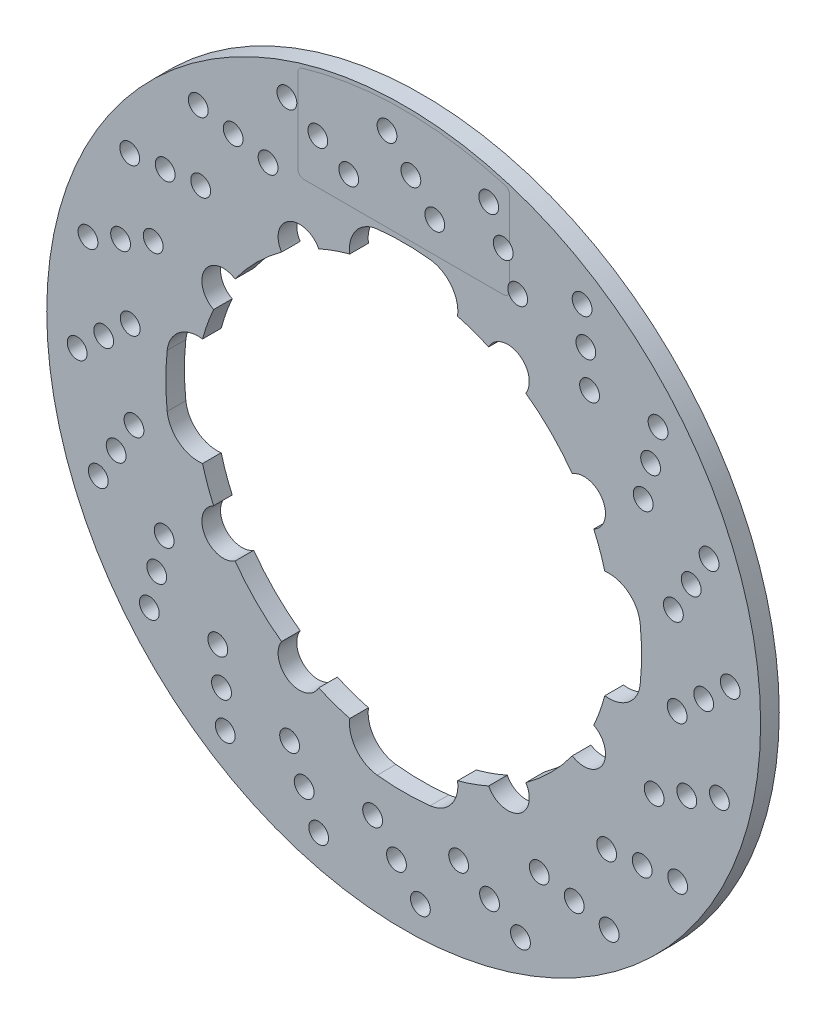
SolidWorks part; units mm, degrees
ref_plane "Front Plane" through (0, 0, 0) normal (0, 0, 1) x (1, 0, 0)
ref_plane "Top Plane" through (0, 0, 0) normal (0, 1, 0) x (1, 0, 0)
ref_plane "Right Plane" through (0, 0, 0) normal (1, 0, 0) x (0, 0, -1)
sketch "Sketch1" plane through (0, 0, 0) normal (0, 0, 1) x (1, 0, 0)
  circle A0 centre (0, 0) radius 114.3
  circle A1 centre (0, 0) radius 76.2
  point P9 (0, 79.756)
  dimension "D1" = 228.6
  dimension "D2" = 152.4
extrude "Boss-Extrude1" add sketch "Sketch1" along normal blind 5.969
sketch "Sketch2" plane through (0, 0, 5.969) normal (0, 0, 1) x (1, 0, 0)
  line L0 (-89.817, 76.2) -> (89.817, 76.2) construction
  line L1 (0, 76.2) -> (-47.8267, 103.8128) construction
  circle A1 centre (0, 0) radius 76.2 construction
  circle A2 centre (0, 0) radius 114.3 construction
  circle A3 centre (-37.395, 97.79) radius 3.175
  circle A4 centre (-27.4963, 92.075) radius 3.175
  circle A5 centre (-17.5976, 86.36) radius 3.175
  point P3 (0, 76.2)
  dimension "D2" = 6.35
  dimension "D3" = 11.43
  dimension "D1" = 30
  dimension "D4" = 11.43
  dimension "D5" = 20.32
extrude "Cut-Extrude1" cut sketch "Sketch2" against normal blind 12.7
sketch "Sketch4" plane through (0, 0, 0) normal (1, 0, 0) x (0, 0, -1)
  line L0 (0, 0) -> (-59.1045, 0) construction
pattern_circular "CirPattern5" count 20 over 360 about axis through (0, 0, 0) along (0, 0, 1) of "Cut-Extrude1"
sketch "Sketch9" plane through (0, 0, 0) normal (0, 0, -1) x (-1, 0, 0)
  line L0 (0, 76.2) -> (0, 42.5) construction
  line L1 (7.427, 41.4562) -> (12.1724, 75.2215)
  line L2 (-7.427, 41.4562) -> (-12.1724, 75.2215)
  circle A0 centre (0, 0) radius 76.2 construction
  arc A1 (-7.427, 41.4562) -> (7.427, 41.4562) centre (0, 42.5) ccw
  circle A2 centre (0, 42.5) radius 4.5
  arc A6 (12.1724, 75.2215) -> (-12.1724, 75.2215) centre (0, 0) ccw
  dimension "D2" = 15
  dimension "D3" = 9
  dimension "D4" = 8
  dimension "D5" = 8
extrude "Boss-Extrude4" add sketch "Sketch9" against normal blind 5.969
fillet "Fillet1" radius 6.35 2 edges at (12.1724, 75.2215, 2.9845) (-12.1724, 75.2215, 2.9845)
pattern_circular "CirPattern8" count 5 over 360 about axis through (0, 0, 0) along (0, 0, 1) of "Fillet1", "Boss-Extrude4"
sketch "Sketch10" plane through (0, 0, 5.969) normal (0, 0, 1) x (1, 0, 0)
  line L0 (0, 114.3) -> (0, 113.03) construction
  circle A0 centre (0, 0) radius 114.3 construction
  circle A1 centre (0, -1.4601) radius 114.4901
  dimension "D2" = 228.9801
  dimension "D1" = 1.27
sketch "Sketch11" plane through (0, 0, 5.969) normal (0, 0, 1) x (1, 0, 0)
  line L0 (0, 113.03) -> (33.9, 113.03) construction
  line L2 (-33.9, 106.4121) -> (-33.9, 79.73)
  line L3 (-31.9, 77.73) -> (31.9, 77.73)
  line L4 (33.9, 106.4121) -> (33.9, 79.73)
  line L6 (0, 114.3) -> (0, 113.03) construction
  arc A0 (-32.4672, 108.33) -> (32.4672, 108.33) centre (0, -1.4601) cw
  circle A1 centre (0, 0) radius 114.3 construction
  arc A2 (-33.9, 79.73) -> (-31.9, 77.73) centre (-31.9, 79.73) ccw
  arc A3 (31.9, 77.73) -> (33.9, 79.73) centre (31.9, 79.73) ccw
  arc A4 (32.4672, 108.33) -> (33.9, 106.4121) centre (31.9, 106.4121) cw
  arc A5 (-32.4672, 108.33) -> (-33.9, 106.4121) centre (-31.9, 106.4121) ccw
  dimension "D3" = 2
  dimension "D6" = 114.4901
  dimension "D1" = 1.27
  dimension "D2" = 67.8
  dimension "D4" = 35.3
  dimension "D5" = 30.6
sketch "Sketch13" plane through (0, 0, 0) normal (0, 0, -1) x (-1, 0, 0)
  line L0 (0, 113.03) -> (33.9, 113.03) construction
  line L2 (-33.9, 106.4121) -> (-33.9, 79.73)
  line L3 (-31.9, 77.73) -> (31.9, 77.73)
  line L4 (33.9, 106.4121) -> (33.9, 79.73)
  line L6 (0, 114.3) -> (0, 113.03) construction
  arc A0 (-32.4672, 108.33) -> (32.4672, 108.33) centre (0, -1.4601) cw
  arc A2 (-33.9, 79.73) -> (-31.9, 77.73) centre (-31.9, 79.73) ccw
  arc A3 (31.9, 77.73) -> (33.9, 79.73) centre (31.9, 79.73) ccw
  arc A4 (32.4672, 108.33) -> (33.9, 106.4121) centre (31.9, 106.4121) cw
  arc A5 (-32.4672, 108.33) -> (-33.9, 106.4121) centre (-31.9, 106.4121) ccw
  dimension "D3" = 2
  dimension "D6" = 114.4901
  dimension "D2" = 67.8
  dimension "D4" = 35.3
  dimension "D5" = 30.6
split line "Split Line1"
split line "Split Line2"
sketch "Sketch14" plane through (0, 0, 0) normal (0, 0, 1) x (1, 0, 0)
  circle A0 centre (0, 0) radius 76.2
  circle A1 centre (0, 0) radius 34.925
  dimension "D1" = 152.4
  dimension "D2" = 69.85
extrude "Boss-Extrude6" add sketch "Sketch14" along normal blind 5.969
sketch "Sketch16" plane through (0, 0, 0) normal (0, 0, 1) x (1, 0, 0)
  line L0 (0, 76.2) -> (0, 42.5) construction
  circle A2 centre (0, 42.5) radius 4.5
  dimension "D3" = 9
extrude "Cut-Extrude3" cut sketch "Sketch16" along normal blind 5.969
pattern_circular "CirPattern9" count 5 over 360 about axis through (0, 0, 5.969) along (0, 0, -1) of "Cut-Extrude3" reverse direction yes
sketch "Sketch17" plane through (0, 0, 0) normal (0, 0, -1) x (-1, 0, 0)
  line L0 (0, 0) -> (0, 66.675) construction
  line L1 (0, 0) -> (-33.3375, 57.7422) construction
  line L2 (0, 0) -> (-57.7422, 33.3375) construction
  circle A0 centre (0, 0) radius 66.675
  circle A1 centre (-33.3375, 57.7422) radius 6.88
  circle A4 centre (-57.7422, 33.3375) radius 6.88
  dimension "D5" = 13.76
  dimension "D1" = 66.675
  dimension "D3" = 30
  dimension "D4" = 30
extrude "Cut-Extrude4" cut sketch "Sketch17" against normal blind 5.969 contours A0 A1 | A0 A4 | A0 A4 | A0 A1 | A4 A0 A1 region at (-0.4578, -0.4578, 0) region at (31.846, 55.1589, 0) region at (34.765, 60.2148, 0) region at (60.2148, 34.765, 0) region at (55.1589, 31.846, 0)
pattern_circular "CirPattern10" count 4 over 360 about axis through (0, 0, 0) along (0, 0, 1) of "Cut-Extrude4"
sketch "Sketch19" plane through (0, 0, 0) normal (0, 0, -1) x (-1, 0, 0)
  line L0 (0, 0) -> (-19.722, 73.6035)
  line L1 (0, 0) -> (19.722, 73.6035)
  line L2 (0, 0) -> (0, 76.2) construction
  circle A0 centre (0, 0) radius 76.2
  circle A2 centre (0, 0) radius 66.675
  arc A3 (27.2097, 60.8703) -> (-27.2097, 60.8703) centre (0, 0) ccw construction
  dimension "D1" = 152.4
  dimension "D2" = 30
  dimension "D3" = 15
extrude "Cut-Extrude6" cut sketch "Sketch19" against normal through all contours A2 L2 A0 L0 | L2 A2 L1 A0 region at (9.3116, 70.7289, 0) region at (-9.3116, 70.7289, 0)
fillet "Fillet2" radius 10 2 edges at (-19.722, 73.6035, 2.9845) (19.722, 73.6035, 2.9845)
pattern_circular "CirPattern11" count 4 over 360 about axis through (0, 0, 5.969) along (0, 0, -1) of "Fillet2", "Cut-Extrude6"
equation "\"D3@Sketch19\"=\"D2@Sketch19\"/2"
